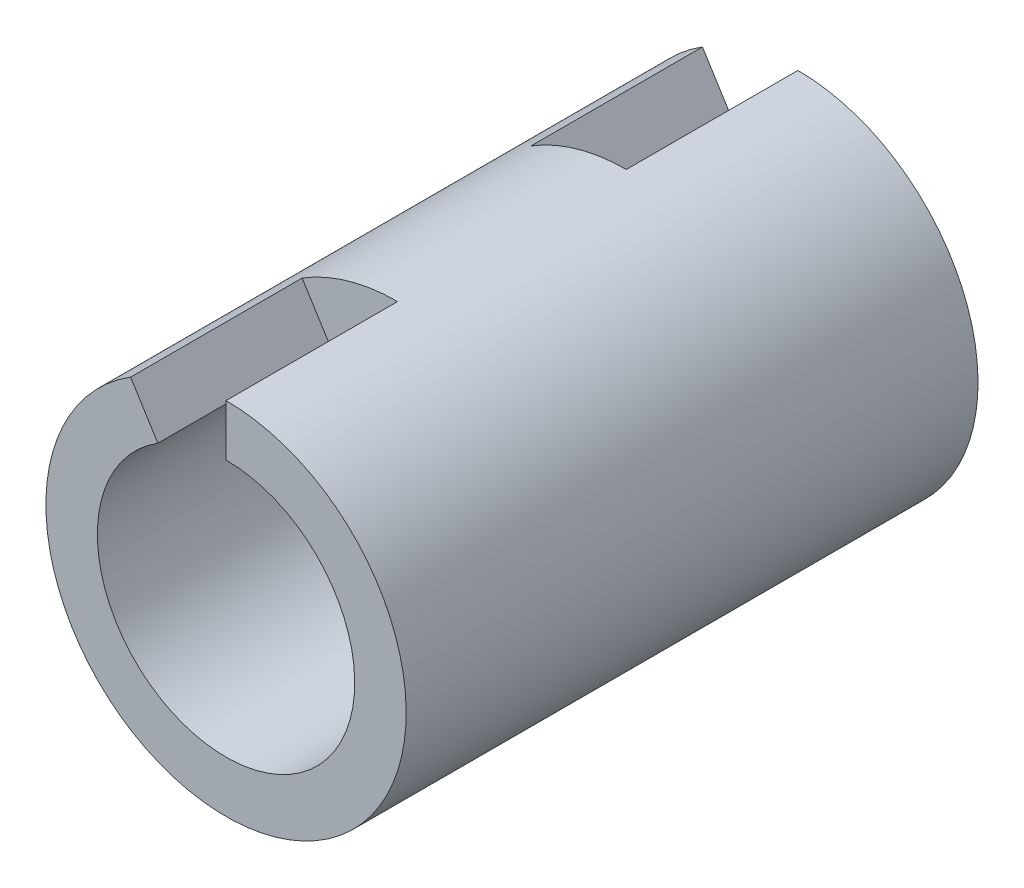
SolidWorks part; units mm, degrees
ref_plane "Front" through (0, 0, 0) normal (0, 0, 1) x (1, 0, 0)
ref_plane "Top" through (0, 0, 0) normal (0, 1, 0) x (1, 0, 0)
ref_plane "Right" through (0, 0, 0) normal (1, 0, 0) x (0, 0, -1)
sketch "Sketch1" plane through (0, 0, 0) normal (0, 0, 1) x (1, 0, 0)
  circle A0 centre (0, 0) radius 6.5
  circle A1 centre (0, 0) radius 4.5
  dimension "D1" = 13
  dimension "D2" = 9
extrude "Boss-Extrude1" add sketch "Sketch1" along normal blind 10 and the other way blind 10
ref_point "Point1"
ref_point "Point2"
ref_axis "Axis1" through (0, 0, 10) along (0, 1, 0)
ref_axis "Axis2" through (0, 0, -10) along (0, 1, 0)
sketch "Sketch2" plane through (0, 0, 10) normal (0, 0, 1) x (1, 0, 0)
  line L0 (-6.23, 9.9701) -> (0, 0)
  line L1 (0, 0) -> (0, 7.5386) construction
  line L3 (0, 0) -> (0, 11.7566)
  arc A0 (0, 11.7566) -> (-6.23, 9.9701) centre (0, 0) ccw
  dimension "D1" = 32
  dimension "D3" = 11.7566
extrude "Cut-Extrude2" cut sketch "Sketch2" against normal blind 6 contours L0 L3 A0
sketch "Sketch3" plane through (0, 0, -10) normal (0, 0, 1) x (1, 0, 0)
  line L0 (-6.23, 9.9701) -> (0, 0)
  line L1 (0, 0) -> (0, 7.5386) construction
  line L3 (0, 0) -> (0, 11.7566)
  arc A0 (0, 11.7566) -> (-6.23, 9.9701) centre (0, 0) ccw
  circle A1 centre (0, 0) radius 4.5 construction
  dimension "D1" = 32
  dimension "D3" = 11.7566
extrude "Cut-Extrude3" cut sketch "Sketch3" along normal blind 6 contours L3 A0 L0
sketch "Sketch4" plane through (0, 0, -10) normal (0, 0, -1) x (-1, 0, 0)
  circle A0 centre (0, 0) radius 6.5
  circle A1 centre (0, 0) radius 6.3
  dimension "D2" = 12.6
  dimension "D1" = 0.2
extrude "Cut-Extrude4" cut sketch "Sketch4" against normal through all
